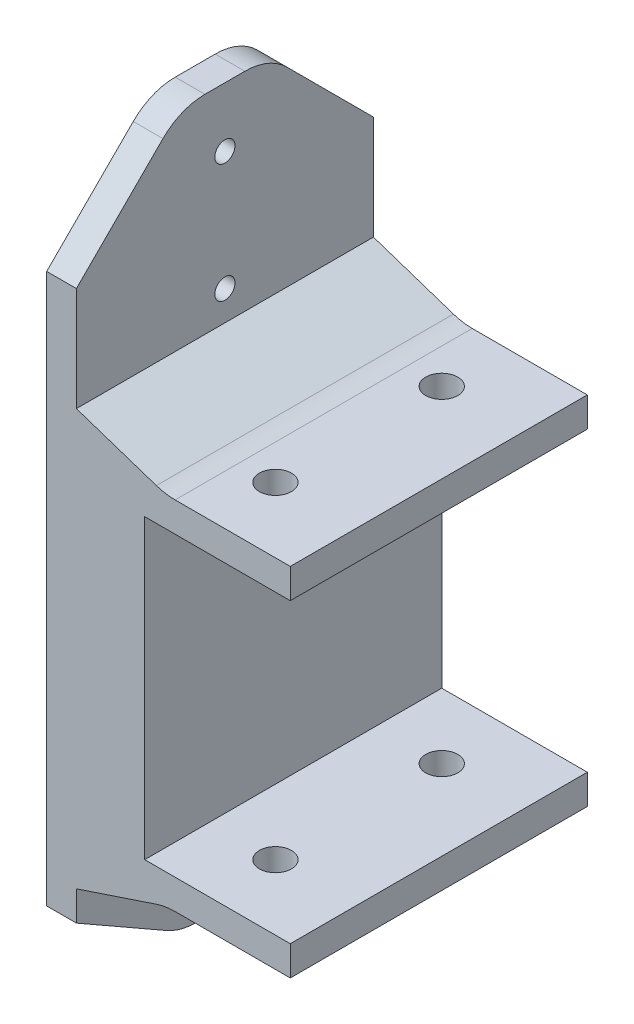
SolidWorks part; units mm, degrees
ref_plane "Front Plane" through (0, 0, 0) normal (0, 0, 1) x (1, 0, 0)
ref_plane "Top Plane" through (0, 0, 0) normal (0, 1, 0) x (1, 0, 0)
ref_plane "Right Plane" through (0, 0, 0) normal (1, 0, 0) x (0, 0, -1)
sketch "Sketch1" plane through (0, 0, 0) normal (0, 0, 1) x (1, 0, 0)
  line L0 (0, 0) -> (0, -5)
  line L1 (0, -5) -> (-36, -5)
  line L2 (-36, -5) -> (-36, -25)
  line L3 (-36, -25) -> (-41, -25)
  line L4 (-41, -25) -> (-41, 95)
  line L5 (-41, 95) -> (-36, 95)
  line L6 (-36, 95) -> (-36, 55)
  line L7 (-36, 55) -> (0, 55)
  line L8 (0, 55) -> (0, 50)
  line L9 (0, 50) -> (-24.5, 50)
  line L10 (-24.5, 50) -> (-24.5, 0)
  line L11 (-24.5, 0) -> (0, 0)
  point P3 (0, 0)
  dimension "D1" = 24.5
  dimension "D2" = 16.5
  dimension "D3" = 50
  dimension "D4" = 5
  dimension "D5" = 5
  dimension "D6" = 20
  dimension "D7" = 40
extrude "Boss-Extrude1" add sketch "Sketch1" along normal blind 50
sketch "Sketch3" plane through (-36, 0, 0) normal (1, 0, 0) x (0, 0, -1)
  line L0 (-50, 55) -> (-50, 77.5)
  line L1 (-50, 55) -> (-50, 95) construction
  line L2 (-50, 77.5) -> (-32.5, 95)
  line L3 (-50, 95) -> (0, 95) construction
  line L4 (-32.5, 95) -> (-17.5, 95)
  line L5 (-17.5, 95) -> (0, 77.5)
  line L6 (0, 55) -> (0, 95) construction
  line L7 (0, 77.5) -> (0, 55)
  line L8 (0, 55) -> (-50, 55)
  line L9 (-50, -5) -> (-50, -15)
  line L10 (-50, -25) -> (-50, -5) construction
  line L11 (-50, -15) -> (-32.5, -25)
  line L12 (-32.5, -25) -> (-17.5, -25)
  line L13 (-50, -25) -> (0, -25) construction
  line L14 (-17.5, -25) -> (0, -15)
  line L15 (0, -25) -> (0, -5) construction
  line L16 (0, -15) -> (0, -5)
  line L17 (0, -5) -> (-50, -5)
  line L19 (-50, 55) -> (0, 55)
  line L20 (-50, 55) -> (-50, 95)
  line L21 (-50, 95) -> (0, 95)
  line L22 (0, 55) -> (0, 95)
  line L23 (-50, -25) -> (0, -25)
  line L24 (-50, -25) -> (-50, -5)
  line L25 (-50, -5) -> (0, -5)
  line L26 (0, -25) -> (0, -5)
  circle A0 centre (-25, 65) radius 1.7
  circle A1 centre (-25, 85) radius 1.7
  circle A2 centre (-25, -15) radius 1.7
  point P40 (0, 0)
  point P41 (-25, -25)
  point P42 (0, 0)
  point P43 (0, 0)
  point P44 (0, 65)
  point P45 (0, -15)
  line M13 (0, 55) -> (0, 95)
  line M14 (0, 95) -> (-50, 95)
  line M15 (-50, 95) -> (-50, 55)
  dimension "D3" = 3.4
  dimension "D1" = 15
  dimension "D2" = 15
  dimension "D4" = 10
  dimension "D5" = 20
  dimension "D6" = 10
  dimension "D7" = 135
extrude "Cut-Extrude1" cut sketch "Sketch3" against normal through all contours L2 M15 M14 | L5 M14 M13 | L24 L23 L11 | L23 L26 L14 | A2 | A1 | A0 region at (-36, 89.1667, 44.1667) region at (-36, 89.1667, 5.8333) region at (-36, -21.6667, 44.1667) region at (-36, -21.6667, 5.8333) region at (-36, -15, 25)
chamfer "Chamfer1" distance 5 distance2 15 1 edges at (-36, -5, 25) first distance on face at (-36, -13.3, 25)
chamfer "Chamfer2" distance 15 distance2 5 1 edges at (-36, 55, 25) first distance on face at (-18, 55, 25)
fillet "Fillet1" radius 10 6 edges at (-21, -5, 25) (-21, 55, 25) (-38.5, -25, 32.5) (-38.5, -25, 17.5) (-38.5, 95, 32.5) (-38.5, 95, 17.5)
sketch "Sketch5" plane through (0, 0, 0) normal (0, 1, 0) x (1, 0, 0)
  line L0 (-24.5, -50) -> (-24.5, 0) construction
  line L1 (0, 0) -> (-19.3772, 0) construction
  line L2 (0, -50) -> (-19.3772, -50) construction
  circle A0 centre (-13.5, -11) radius 2.7
  circle A1 centre (-13.5, -39) radius 2.7
  point P4 (0, 0)
  dimension "D2" = 5.4
  dimension "D1" = 11
  dimension "D3" = 11
  dimension "D4" = 11
extrude "Cut-Extrude2" cut sketch "Sketch5" against normal through all both and the other way through all
